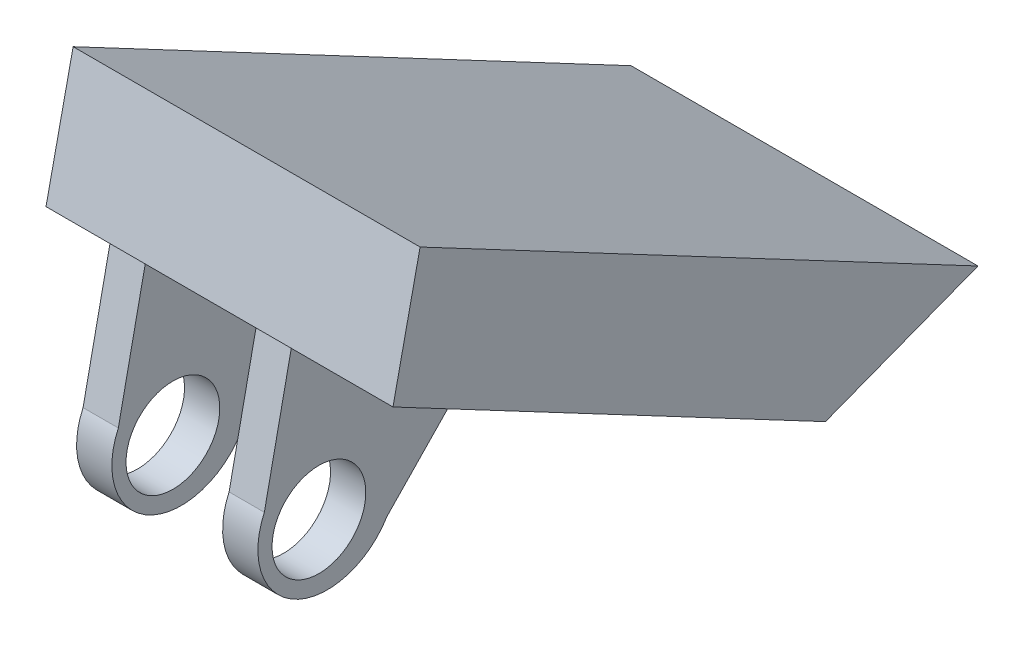
SolidWorks part; units mm, degrees
ref_plane "Front Plane" through (0, 0, 0) normal (0, 0, 1) x (1, 0, 0)
ref_plane "Top Plane" through (0, 0, 0) normal (0, 1, 0) x (1, 0, 0)
ref_plane "Right Plane" through (0, 0, 0) normal (1, 0, 0) x (0, 0, -1)
ref_plane "Plane1" through (80.0832, 0, 0) normal (1, 0, 0) x (0, 0, -1)
ref_plane "Plane2" through (87.7788, 0, 0) normal (1, 0, 0) x (0, 0, -1)
ref_plane "Plane3" through (113.0071, 0, 0) normal (1, 0, 0) x (0, 0, -1)
sketch "Sketch1" plane through (80.0832, 0, 0) normal (1, 0, 0) x (0, 0, -1)
  line L0 (267.4874, 138.174) -> (272.1745, 159.7614)
  line L1 (272.1745, 159.7614) -> (368.557, 108.7295)
  line L2 (368.557, 108.7295) -> (342.2053, 98.6155)
  line L3 (342.2053, 98.6155) -> (267.4874, 138.174)
extrude "Boss-Extrude1" add sketch "Sketch1" along normal blind 59.9415
sketch "Sketch2" plane through (87.7788, 0, 0) normal (1, 0, 0) x (0, 0, -1)
  line L0 (271.2382, 136.7211) -> (266.1933, 112.5934)
  line L1 (271.2382, 136.7211) -> (304.4896, 119.1153)
  line L2 (304.4896, 119.1153) -> (287.3698, 101.3811)
  arc A0 (266.1933, 112.5934) -> (287.3698, 101.3811) centre (277.0756, 107.5426) ccw
  circle A1 centre (275.621, 106.806) radius 8.0999
  point P2 (271.4615, 96.9399)
  point P8 (267.6208, 105.539)
extrude "Boss-Extrude2" add sketch "Sketch2" along normal blind 6.0922
extrude "Boss-Extrude3" add sketch "Sketch2<2>" along normal blind 6.0922 from surface starting at plane "Plane3"
sketch "Sketch2<2>" plane through (87.7788, 0, 0) normal (1, 0, 0) x (0, 0, -1) same geometry as "Sketch2"
